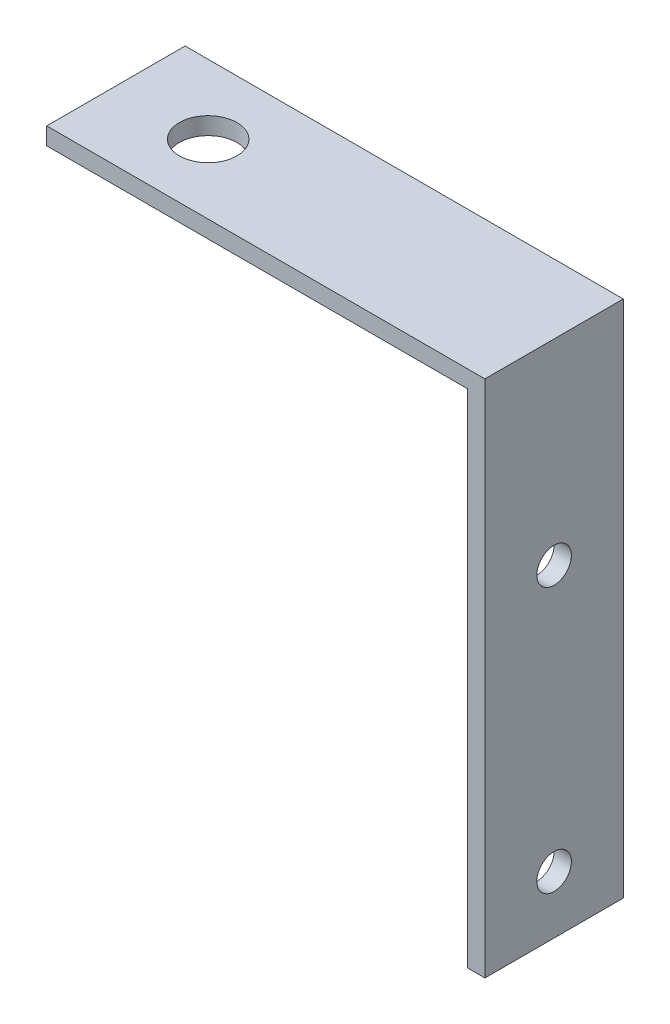
SolidWorks part; units mm, degrees
material "1060 Alloy"
ref_plane "Front Plane" through (0, 0, 0) normal (0, 0, 1) x (1, 0, 0)
ref_plane "Top Plane" through (0, 0, 0) normal (0, 1, 0) x (1, 0, 0)
ref_plane "Right Plane" through (0, 0, 0) normal (1, 0, 0) x (0, 0, -1)
sketch "Sketch1" plane through (0, 0, 0) normal (0, 1, 0) x (1, 0, 0)
  line L0 (17.5, 6) -> (17.5, -6)
  line L1 (-19, -6) -> (19, -6)
  line L2 (-19, -6) -> (-19, 6)
  line L3 (-19, 6) -> (19, 6)
  line L4 (19, -6) -> (19, 6)
  line L5 (-19, -6) -> (19, 6) construction
  line L6 (-19, 6) -> (19, -6) construction
  point P0 (0, 0)
  dimension "D1" = 38
  dimension "D2" = 12
  dimension "D3" = 1.5
extrude "Boss-Extrude1" add sketch "Sketch1" against normal blind 1.5 contours L3 L2 L1 L0 region at (-0.75, 0, 0)
extrude "Boss-Extrude2" add sketch "Sketch1<3>" against normal blind 45 contours L1 L4 L3 L0 region at (18.25, 0, 0)
sketch "Sketch1<3>" plane through (0, 0, 0) normal (0, 1, 0) x (1, 0, 0) same geometry as "Sketch1"
sketch "Sketch2" plane through (19, 0, 0) normal (1, 0, 0) x (0, 0, -1)
  line L0 (-6, 0) -> (6, 0) construction
  line L1 (-6, -45) -> (6, -45) construction
  circle A0 centre (0, -40) radius 1.5
  circle A1 centre (0, -17) radius 1.5
  point P7 (0, 0)
  dimension "D1" = 3
  dimension "D2" = 5
  dimension "D3" = 23
extrude "Cut-Extrude1" cut sketch "Sketch2" against normal through all
sketch "Sketch3" plane through (0, 0, 0) normal (0, 1, 0) x (1, 0, 0)
  line L0 (19, -6) -> (19, 6) construction
  circle A0 centre (-11, 0) radius 2.5
  dimension "D2" = 5
  dimension "D1" = 30
extrude "Cut-Extrude2" cut sketch "Sketch3" against normal blind 30
